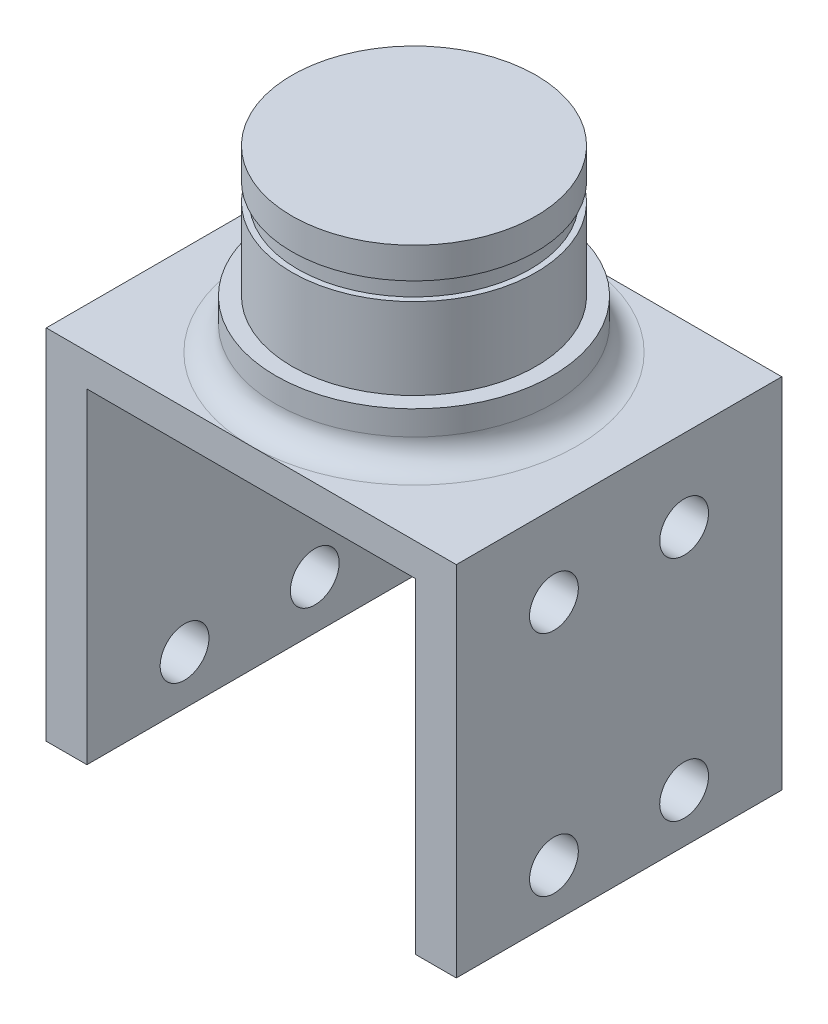
SolidWorks part; units mm, degrees
material "6061 合金"
ref_plane "前视基准面" through (0, 0, 0) normal (0, 0, 1) x (1, 0, 0)
ref_plane "上视基准面" through (0, 0, 0) normal (0, 1, 0) x (1, 0, 0)
ref_plane "右视基准面" through (0, 0, 0) normal (1, 0, 0) x (0, 0, -1)
sketch "草图1" plane through (0, 0, 0) normal (0, 1, 0) x (1, 0, 0)
  line L1 (12.6, 10) -> (-12.6, 10)
  line L2 (12.6, 10) -> (12.6, -10)
  line L3 (12.6, -10) -> (-12.6, -10)
  line L4 (-12.6, 10) -> (-12.6, -10)
  line L5 (12.6, 10) -> (-12.6, -10) construction
  line L6 (12.6, -10) -> (-12.6, 10) construction
  point P0 (0, 0)
  dimension "D1" = 20
  dimension "D2" = 25.2
extrude "凸台-拉伸1" add sketch "草图1" along normal blind 2
sketch "草图2" plane through (0, 0, 0) normal (0, -1, 0) x (1, 0, 0)
  line L0 (0, 0) -> (0, -10) construction
  line L1 (-10.1, 10) -> (-12.6, 10)
  line L2 (-10.1, 10) -> (-10.1, -10)
  line L3 (-10.1, -10) -> (-12.6, -10)
  line L4 (-12.6, 10) -> (-12.6, -10)
  line L5 (-10.1, 10) -> (-12.6, -10) construction
  line L6 (-10.1, -10) -> (-12.6, 10) construction
  line L7 (12.6, -10) -> (-12.6, -10) construction
  line L8 (10.1, -10) -> (12.6, -10)
  line L9 (12.6, 10) -> (12.6, -10)
  line L10 (10.1, 10) -> (12.6, 10)
  line L11 (10.1, 10) -> (10.1, -10)
  point P0 (-11.35, 0)
  dimension "D1" = 2.5
extrude "凸台-拉伸2" add sketch "草图2" along normal blind 20
sketch "草图3" plane through (12.6, 0, 0) normal (1, 0, 0) x (0, 0, -1)
  line L0 (0, -20) -> (0, -10) construction
  line L1 (10, -20) -> (-10, -20) construction
  line L2 (0, -10) -> (-10, -10) construction
  line L3 (4, -3) -> (-4, -3) construction
  line L4 (4, -3) -> (4, -17) construction
  line L5 (4, -17) -> (-4, -17) construction
  line L6 (-4, -3) -> (-4, -17) construction
  line L7 (4, -3) -> (-4, -17) construction
  line L8 (4, -17) -> (-4, -3) construction
  line L9 (-10, 2) -> (-10, -20) construction
  circle A0 centre (-4, -17) radius 1.5
  circle A1 centre (4, -17) radius 1.5
  circle A2 centre (4, -3) radius 1.5
  circle A3 centre (-4, -3) radius 1.5
  dimension "D4" = 3
  dimension "D1" = 10
  dimension "D2" = 14
  dimension "D3" = 8
extrude "切除-拉伸1" cut sketch "草图3" against normal through all
sketch "草图4" plane through (0, 2, 0) normal (0, 1, 0) x (1, 0, 0)
  circle A0 centre (0, 0) radius 8.5
  dimension "D1" = 17
extrude "凸台-拉伸3" add sketch "草图4" along normal blind 3
sketch "草图5" plane through (0, 5, 0) normal (0, 1, 0) x (1, 0, 0)
  circle A0 centre (0, 0) radius 7.5
  dimension "D1" = 15
extrude "凸台-拉伸4" add sketch "草图5" along normal blind 8 contours A0
sketch "草图6" plane through (0, 13, 0) normal (0, 1, 0) x (1, 0, 0)
  circle A0 centre (0, 0) radius 7
  dimension "D1" = 14
extrude "凸台-拉伸5" add sketch "草图6" along normal blind 18
sketch "草图10" plane through (0, 31, 0) normal (0, 1, 0) x (1, 0, 0)
  line L1 (6, 6) -> (-6, 6)
  line L2 (6, 6) -> (6, -6)
  line L3 (6, -6) -> (-6, -6)
  line L4 (-6, 6) -> (-6, -6)
  line L5 (6, 6) -> (-6, -6) construction
  line L6 (6, -6) -> (-6, 6) construction
  circle A0 centre (0, 0) radius 9.3197
  point P0 (0, 0)
extrude "切除-拉伸4" cut sketch "草图10" against normal blind 15
fillet "圆角2" radius 1.5 1 edges at (0, 2, 8.5)
sketch "草图12" plane through (0, 13, 0) normal (0, 1, 0) x (1, 0, 0)
  circle A0 centre (0, 0) radius 7.5
extrude "切除-拉伸5" cut sketch "草图12" along normal blind 26
sketch "草图13" plane through (0, 0, 0) normal (1, 0, 0) x (0, 0, -1)
  line L0 (7.5, 11.1) -> (7.15, 11.1)
  line L1 (7.5, 5) -> (7.5, 13) construction
  line L2 (7.15, 11.1) -> (7.15, 10)
  line L3 (7.15, 10) -> (7.5, 10)
  line L4 (8.5, 5) -> (-8.5, 5) construction
  line L5 (7.5, 10) -> (7.5, 11.1)
  point P8 (7.325, 10)
  dimension "D1" = 0.35
  dimension "D2" = 1.1
  dimension "D3" = 5
ref_axis "基准轴1" through (0, 13, 0) along (0, -1, 0)
revolve "切除-旋转1" cut sketch "草图13" angle 360 about axis through (0, 13, 0) along (0, -1, 0)
